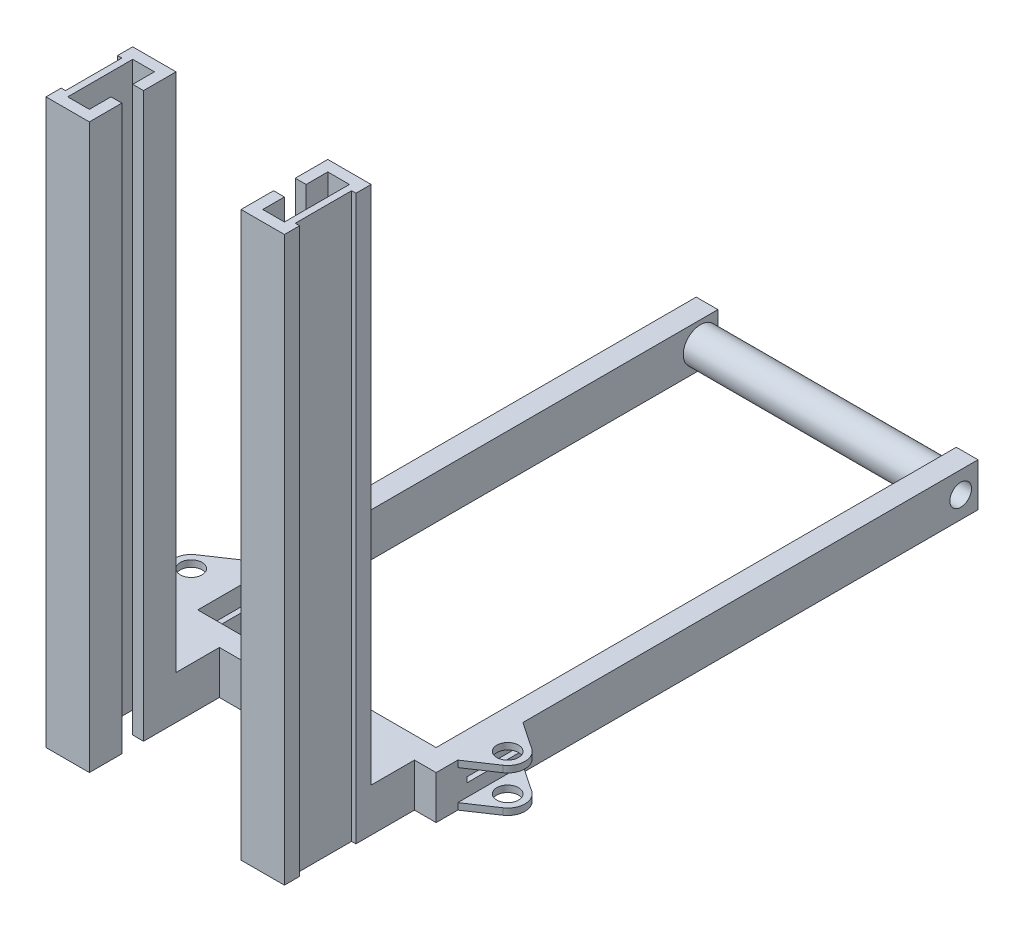
SolidWorks part; units mm, degrees
ref_plane "前基準面" through (0, 0, 0) normal (0, 0, 1) x (1, 0, 0)
ref_plane "上基準面" through (0, 0, 0) normal (0, 1, 0) x (1, 0, 0)
ref_plane "右基準面" through (0, 0, 0) normal (1, 0, 0) x (0, 0, -1)
sketch "草圖3" plane through (0, 0, 0) normal (0, 1, 0) x (1, 0, 0)
  line L0 (-300, 0) -> (300, 0) construction
  line L5 (0, 0) -> (0, 646.511) construction
  line L6 (-325, 600) -> (-275, 600)
  line L7 (-325, 600) -> (-325, -600)
  line L8 (-325, -600) -> (-275, -600)
  line L9 (-275, 600) -> (-275, -600)
  line L10 (-325, 600) -> (-275, -600) construction
  line L11 (-325, -600) -> (-275, 600) construction
  line L12 (325, -600) -> (275, -600)
  line L13 (275, 600) -> (275, -600)
  line L14 (325, 600) -> (275, 600)
  line L15 (325, 600) -> (325, -600)
  point P3 (0, 0)
  dimension "D1" = 50
  dimension "D2" = 1200
  dimension "D3" = 600
extrude "填料-伸長2" add sketch "草圖3" along normal blind 100
sketch "草圖5" plane through (-275, 0, 0) normal (1, 0, 0) x (0, 0, -1)
  line L0 (600, 50) -> (312.0722, 50) construction
  line L1 (600, 100) -> (600, 0) construction
  circle A0 centre (560, 50) radius 25
  circle A1 centre (560, 50) radius 40
  dimension "D2" = 50
  dimension "D3" = 80
  dimension "D1" = 560
extrude "填料-伸長3" add sketch "草圖5" along normal up to surface (550 mm away) up to face at (275, 50, 0)
sketch "草圖6" plane through (0, 0, 0) normal (0, 1, 0) x (1, 0, 0)
  line L3 (-387.2837, -558.218) -> (-325, -600)
  line L6 (-365, -525) -> (-441.8142, -525) construction
  line L7 (-387.2837, -491.782) -> (-325, -450)
  line L8 (-325, -450) -> (-325, -600)
  circle A0 centre (-365, -525) radius 25
  arc A1 (-387.2837, -491.782) -> (-387.2837, -558.218) centre (-365, -525) ccw
  dimension "D1" = 50
  dimension "D2" = 80
extrude "填料-伸長4" add sketch "草圖6" along normal up to surface (100 mm away) up to face at (-300, 100, 0)
extrude "除料-伸長2" cut sketch "草圖6<4>" along normal blind 70 from offset 15
sketch "草圖6<4>" plane through (0, 0, 0) normal (0, 1, 0) x (1, 0, 0) same geometry as "草圖6"
mirror "鏡射3" about plane through (0, 0, 0) normal (1, 0, 0) of "填料-伸長4", "除料-伸長2"
extrude "除料-伸長3" cut sketch "草圖5<3>" against normal blind 65 and the other way blind 950 contours A0 L0 | L0 A0 region at (-275, 39.3897, -560) region at (-275, 60.6103, -560)
sketch "草圖5<3>" plane through (-275, 0, 0) normal (1, 0, 0) x (0, 0, -1) same geometry as "草圖5"
sketch "草圖7" plane through (0, 100, 0) normal (0, 1, 0) x (1, 0, 0)
  line L0 (-365, -525) -> (-215, -525) construction
  dimension "D1" = 150
sketch "草圖11" plane through (0, 100, 0) normal (0, 1, 0) x (1, 0, 0)
  line L0 (-365, -525) -> (-510.1214, -525) construction
  line L1 (-365, -525) -> (-510.6787, -609.1076) construction
  line L2 (-365, -525) -> (-418.7452, -493.9702) construction
  line L3 (-365, -487.5) -> (-275, -447.4294) construction
  line L4 (-275, -600) -> (-275, 600) construction
  line L5 (-365, -562.5) -> (-275, -578.3694) construction
  line L6 (-275, -447.4294) -> (-275, -578.3694)
  line L7 (-275, -447.4294) -> (-325, -447.4294)
  line L8 (-325, 600) -> (-325, -450) construction
  line L9 (-325, -447.4294) -> (-325, -578.3694)
  line L10 (-325, -578.3694) -> (-275, -578.3694)
  circle A0 centre (-365, -525) radius 37.5 construction
  dimension "D2" = 75
  dimension "D1" = 30
  dimension "D3" = 30
  dimension "D4" = 6
  dimension "D5" = 20
extrude "除料-伸長5" cut sketch "草圖11" against normal mid plane 12 from offset 50 offset against normal yes
mirror "鏡射4" about plane through (0, 0, 0) normal (1, 0, 0) of "除料-伸長5"
sketch "草圖12" plane through (0, 100, 0) normal (0, 1, 0) x (1, 0, 0)
  line L1 (-325, -600) -> (325, -600)
  line L2 (-325, -600) -> (-325, -650)
  line L3 (-325, -650) -> (325, -650)
  line L4 (325, -600) -> (325, -650)
  dimension "D1" = 50
extrude "填料-伸長5" add sketch "草圖12" against normal up to surface (100 mm away) up to face at (-331.0405, 0, 214.2857)
sketch "草圖13" plane through (0, 0, 650) normal (0, 0, 1) x (1, 0, 0)
  line L5 (-325, 100) -> (325, 100) construction
  line L6 (-275, 100) -> (-175, 100)
  line L7 (-275, 100) -> (-275, 0)
  line L8 (-275, 0) -> (-175, 0)
  line L9 (-175, 100) -> (-175, 0)
  line L10 (325, 0) -> (-325, 0) construction
  line L11 (-325, 0) -> (-325, 100) construction
  line L12 (0, 0) -> (0, 226.4256) construction
  dimension "D1" = 50
  dimension "D2" = 100
extrude "填料-伸長6" add sketch "草圖13" along normal blind 100
mirror "鏡射5" about plane through (0, 0, 0) normal (1, 0, 0) of "填料-伸長6"
sketch "草圖14" plane through (0, 0, 0) normal (0, 1, 0) x (1, 0, 0)
  line L1 (-275, -750) -> (-175, -750)
  line L2 (-275, -750) -> (-275, -950)
  line L3 (-275, -950) -> (-175, -950)
  line L4 (-175, -750) -> (-175, -950)
  line L5 (-125, -825) -> (-225, -825)
  line L6 (-125, -825) -> (-125, -875)
  line L7 (-125, -875) -> (-225, -875)
  line L8 (-225, -825) -> (-225, -875)
  line L9 (-125, -825) -> (-225, -875) construction
  line L10 (-125, -875) -> (-225, -825) construction
  line L11 (-250, -775) -> (-200, -775)
  line L12 (-250, -775) -> (-250, -925)
  line L13 (-250, -925) -> (-200, -925)
  line L14 (-200, -775) -> (-200, -925)
  line L15 (-250, -775) -> (-200, -925) construction
  line L16 (-250, -925) -> (-200, -775) construction
  point P5 (-175, -850)
  point P10 (-225, -850)
  point P15 (-187.1061, -825)
  point P16 (0, 0)
  point P18 (-177.9519, -825)
  point P19 (-225, -950)
  dimension "D1" = 200
  dimension "D2" = 150
  dimension "D3" = 50
  dimension "D4" = 50
extrude "填料-伸長7" add sketch "草圖14" along normal blind 1300 contours L11 L14 L5 L4 L1 L2 L3 L7 L13 L12 region at (-225, 0, 752.2361)
mirror "鏡射6" about plane through (0, 0, 0) normal (1, 0, 0) of "填料-伸長7"
sketch "草圖15" plane through (275, 0, 0) normal (1, 0, 0) x (0, 0, -1)
  line L0 (-750, 1300) -> (-950, 1300) construction
  line L1 (-915, 1300) -> (-785, 1300)
  line L2 (-915, 1300) -> (-915, 0)
  line L3 (-915, 0) -> (-785, 0)
  line L4 (-785, 1300) -> (-785, 0)
  line L5 (-950, 0) -> (-650, 0) construction
  line L6 (-950, 1300) -> (-950, 0) construction
  dimension "D1" = 130
  dimension "D2" = 35
extrude "除料-伸長6" cut sketch "草圖15" against normal blind 10
mirror "鏡射7" about plane through (0, 0, 0) normal (1, 0, 0) of "除料-伸長6"
sketch "草圖16" plane through (0, 0, 950) normal (0, 0, 1) x (1, 0, 0)
  line L0 (175, 0) -> (-175, 0) construction
  line L1 (-500, 750) -> (500, 750)
  line L2 (-500, 750) -> (-500, -50)
  line L3 (-500, -50) -> (500, -50)
  line L4 (500, 750) -> (500, -50)
  line L5 (-500, 750) -> (500, -50) construction
  line L6 (-500, -50) -> (500, 750) construction
  line L7 (-470, 720) -> (-470, 440)
  line L8 (-470, -20) -> (470, -20)
  line L9 (470, 720) -> (470, 440)
  line L10 (-470, 720) -> (470, 720)
  line L11 (470, 350) -> (-470, 350) construction
  line L12 (470, 410) -> (-470, 410)
  line L13 (470, 290) -> (-470, 290)
  line L14 (470, 440) -> (375, 440)
  line L15 (470, 260) -> (-470, 260)
  line L16 (0, 720) -> (0, 440) construction
  line L17 (-15, 720) -> (-15, 440)
  line L18 (15, 720) -> (15, 440)
  line L19 (120, 720) -> (120, 440) construction
  line L20 (240, 720) -> (240, 440) construction
  line L21 (360, 720) -> (360, 440) construction
  line L22 (105, 720) -> (105, 440)
  line L23 (225, 720) -> (225, 440)
  line L24 (345, 720) -> (345, 440)
  line L25 (135, 720) -> (135, 440)
  line L26 (255, 720) -> (255, 440)
  line L27 (375, 720) -> (375, 440)
  line L28 (-375, 720) -> (-375, 440)
  line L29 (-345, 720) -> (-345, 440)
  line L30 (-255, 720) -> (-255, 440)
  line L31 (-225, 720) -> (-225, 440)
  line L32 (-135, 720) -> (-135, 440)
  line L33 (-105, 720) -> (-105, 440)
  line L34 (375, -20) -> (375, 260)
  line L35 (345, -20) -> (345, 260)
  line L36 (255, -20) -> (255, 260)
  line L37 (225, -20) -> (225, 260)
  line L38 (135, -20) -> (135, 260)
  line L39 (105, -20) -> (105, 260)
  line L40 (15, -20) -> (15, 260)
  line L41 (-15, -20) -> (-15, 260)
  line L42 (-105, -20) -> (-105, 260)
  line L43 (-135, -20) -> (-135, 260)
  line L44 (-225, -20) -> (-225, 260)
  line L45 (-255, -20) -> (-255, 260)
  line L46 (-375, -20) -> (-375, 260)
  line L47 (-345, -20) -> (-345, 260)
  line L48 (-375, 440) -> (-470, 440)
  line L49 (470, 440) -> (-470, 440) construction
  line L50 (-255, 440) -> (-345, 440)
  line L51 (-135, 440) -> (-225, 440)
  line L52 (-15, 440) -> (-105, 440)
  line L53 (105, 440) -> (15, 440)
  line L54 (225, 440) -> (135, 440)
  line L55 (345, 440) -> (255, 440)
  line L56 (470, 410) -> (470, -20)
  line L57 (470, 720) -> (470, -20) construction
  line L58 (-470, 410) -> (-470, 290)
  line L59 (-470, 720) -> (-470, -20) construction
  line L60 (-470, 260) -> (-470, -20)
  point P0 (0, 350)
  dimension "D1" = 50
  dimension "D2" = 1000
  dimension "D3" = 800
  dimension "D11" = 4
  dimension "D4" = 30
  dimension "D5" = 60
  dimension "D6" = 60
  dimension "D7" = 30
  dimension "D8" = 30
  dimension "D9" = 15
  dimension "D10" = 15
  dimension "D12" = 15
  dimension "D13" = 15
